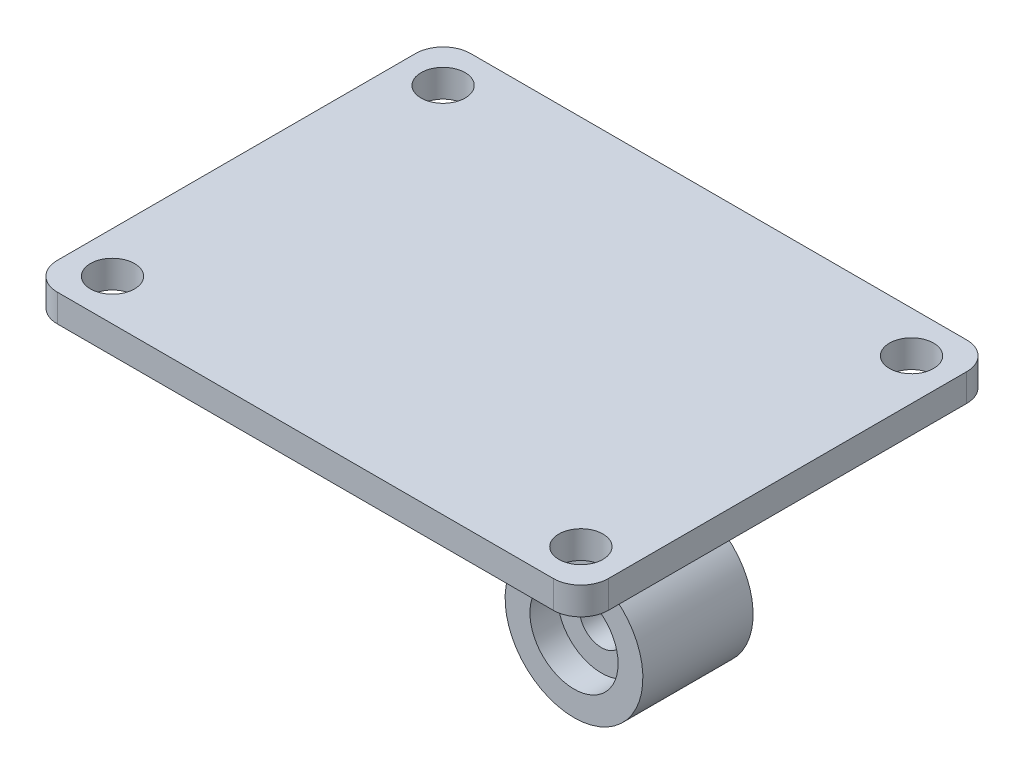
SolidWorks part; units mm, degrees
ref_plane "Front" through (0, 0, 0) normal (0, 0, 1) x (1, 0, 0)
ref_plane "Top" through (0, 0, 0) normal (0, 1, 0) x (1, 0, 0)
ref_plane "Right" through (0, 0, 0) normal (1, 0, 0) x (0, 0, -1)
sketch "Эскиз1" plane through (0, 0, 0) normal (0, 0, 1) x (1, 0, 0)
  line L0 (-12.5, 5) -> (-7.5, 5)
  line L1 (-12.5, 5) -> (-12.5, 13)
  line L2 (-7.5, 5) -> (-7.5, 13)
  line L3 (-12.5, 13) -> (-7.5, 13)
  line L10 (0, 0) -> (-21.0344, 0) construction
  circle A0 centre (-10, 5) radius 5
  circle A2 centre (-10, 5) radius 1.6
  point P2 (-10, 5)
  dimension "D4" = 10
  dimension "D6" = 3.2
  dimension "D1" = 5
  dimension "D2" = 0
  dimension "D3" = 10
  dimension "D5" = 8
extrude "Бобышка-Вытянуть1" add sketch "Эскиз1" against normal blind 8 contours A2 L0 L1 A0 L2 | A2 L0 L2 A0 L1 | A0 L2 L3 L1 region at (-10, 7.7426, 0) region at (-7.95, 4.8632, 0) region at (-10, 11.3855, 0)
sketch "Эскиз2" plane through (0, 0, 0) normal (0, 0, 1) x (1, 0, 0)
  circle A0 centre (-10, 5) radius 3.2
  dimension "D1" = 6.4
extrude "Вырез-Вытянуть1" cut sketch "Эскиз2" against normal blind 2
sketch "Эскиз3" plane through (0, 13, 0) normal (0, 1, 0) x (1, 0, 0)
  line L0 (-2.653, 8) -> (8.3987, 8) construction
  line L1 (-12.5, 8) -> (-7.5, 8) construction
  line L2 (-2.5, 23) -> (-42.5, 23)
  line L3 (-2.5, 23) -> (-2.5, -7)
  line L4 (-2.5, -7) -> (-42.5, -7)
  line L5 (-42.5, 23) -> (-42.5, -7)
  line L6 (-22.5, -7) -> (-22.5, 23) construction
  line L7 (-2.5, 8) -> (-42.5, 8) construction
  point P1 (-22.5, 8)
  dimension "D1" = 30
  dimension "D2" = 40
  dimension "D3" = 7.5
extrude "Бобышка-Вытянуть2" add sketch "Эскиз3" along normal blind 2
extrude "Бобышка-Вытянуть3" add sketch "Эскиз1<3>" against normal blind 16 contours A0 L2 L3 L1 region at (-10, 11.3855, 0)
sketch "Эскиз1<3>" plane through (0, 0, 0) normal (0, 0, 1) x (1, 0, 0) same geometry as "Эскиз1"
fillet "Скругление1" radius 2 4 edges at (-2.5, 14, -23) (-42.5, 14, -23) (-42.5, 14, 7) (-2.5, 14, 7)
sketch "Эскиз4" plane through (0, 13, 0) normal (0, -1, 0) x (1, 0, 0)
  line L0 (-2.5, -23) -> (-2.5, 7) construction
  line L1 (-2.5, 7) -> (-42.5, 7) construction
  line L2 (-5.5, 4) -> (-5.5, -20) construction
  circle A0 centre (-5.5, 4) radius 1.6
  circle A1 centre (-5.5, -20) radius 1.6
  circle A2 centre (-39.5, -20) radius 1.6
  circle A3 centre (-39.5, 4) radius 1.6
  point P6 (0, 0)
  point P7 (0, 0)
  dimension "D1" = 3.2
  dimension "D2" = 3
  dimension "D3" = 3
  dimension "D6" = 24
  dimension "D4" = 2
  dimension "D5" = 2
extrude "Вырез-Вытянуть3" cut sketch "Эскиз4" against normal through all
